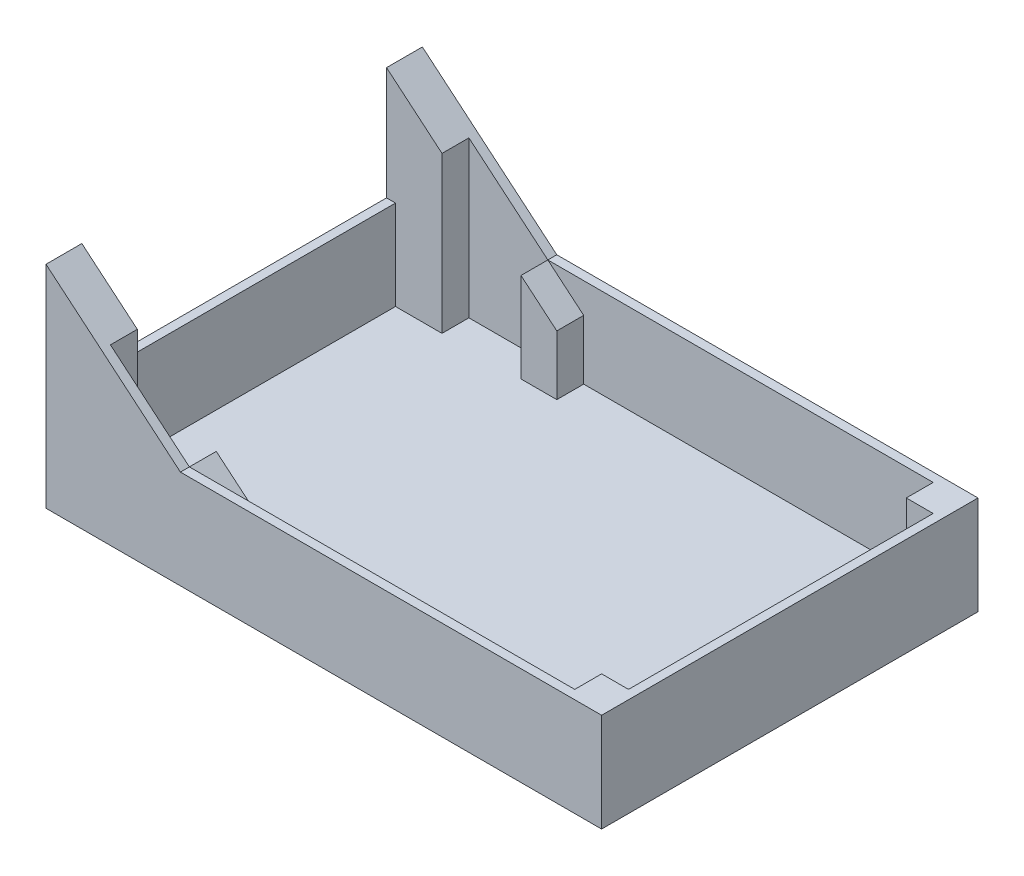
SolidWorks part; units mm, degrees
ref_plane "Front Plane" through (0, 0, 0) normal (0, 0, 1) x (1, 0, 0)
ref_plane "Top Plane" through (0, 0, 0) normal (0, 1, 0) x (1, 0, 0)
ref_plane "Right Plane" through (0, 0, 0) normal (1, 0, 0) x (0, 0, -1)
sketch "Sketch1" plane through (0, 0, 0) normal (0, 1, 0) x (1, 0, 0)
  line L1 (-60, 40) -> (60, 40)
  line L2 (-60, 40) -> (-60, -40)
  line L3 (-60, -40) -> (60, -40)
  line L4 (60, 40) -> (60, -40)
  line L5 (-60, 40) -> (60, -40) construction
  line L6 (-60, -40) -> (60, 40) construction
  point P0 (0, 0)
  dimension "D1" = 120
  dimension "D2" = 80
extrude "Extrude-Thin1" add sketch "Sketch1" along normal blind 20 thin thin type one direction wall 2
sketch "Sketch2" plane through (0, 0, 0) normal (0, -1, 0) x (1, 0, 0)
  line L4 (62, -42) -> (62, 42)
  line L5 (62, 42) -> (-62, 42)
  line L6 (-62, 42) -> (-62, -42)
  line L7 (-62, -42) -> (62, -42)
  line L8 (62, -42) -> (62, 42)
  line L9 (62, 42) -> (-62, 42)
  line L10 (-62, 42) -> (-62, -42)
  line L11 (-62, -42) -> (62, -42)
  dimension "D1" = 0
extrude "Boss-Extrude1" add sketch "Sketch2" along normal blind 2 contours L8 L9 L10 L11
sketch "Sketch3" plane through (0, 0, -40) normal (0, 0, 1) x (1, 0, 0)
  line L2 (-24, 13.2872) -> (-24, -2)
  line L3 (-24, -2) -> (-32, -2)
  line L4 (-32, 20) -> (-32, -2)
  line L5 (-62, 20) -> (-62, -2) construction
  line L6 (-62, -2) -> (62, -2) construction
  line L7 (-32, 20) -> (-24, 13.2872)
  dimension "D1" = 8
  dimension "D3" = 30
extrude "Boss-Extrude2" add sketch "Sketch3" along normal blind 6
ref_plane "Plane1" through (0, 0, 0) normal (0, 0, -1) x (-1, 0, 0)
sketch "Sketch9" plane through (0, 20, 0) normal (0, 1, 0) x (1, 0, 0)
  line L1 (60, 40) -> (54, 40)
  line L2 (60, 40) -> (60, 34)
  line L3 (60, 34) -> (54, 34)
  line L4 (54, 40) -> (54, 34)
  line L5 (60, -40) -> (54, -40)
  line L6 (60, -40) -> (60, -34)
  line L7 (60, -34) -> (54, -34)
  line L8 (54, -40) -> (54, -34)
  dimension "D1" = 6
  dimension "D2" = 6
  dimension "D3" = 6
  dimension "D4" = 6
extrude "Boss-Extrude7" add sketch "Sketch9" against normal up to surface (20 mm away) up to face at (-14, 0, -18.5)
sketch "Sketch10" plane through (0, 0, -42) normal (0, 0, -1) x (-1, 0, 0)
  line L0 (62, 20) -> (62, 45.173)
  line L1 (62, 45.173) -> (32, 20)
  line L2 (-62, 20) -> (62, 20) construction
  line L3 (32, 20) -> (62, 20)
  dimension "D1" = 40
extrude "Boss-Extrude8" add sketch "Sketch10" against normal blind 2
sketch "Sketch11" plane through (0, 0, -42) normal (0, 0, -1) x (-1, 0, 0)
  line L1 (62, 45.173) -> (32, 20) construction
  line L4 (62, 45.173) -> (49.619, 34.7841)
  line L5 (62, 45.173) -> (62, -2)
  line L6 (62, -2) -> (-62, -2) construction
  line L7 (49.619, -2) -> (62, -2)
  line L8 (49.619, 34.7841) -> (49.619, -2)
  line L9 (62, 45.173) -> (62, -2) construction
  dimension "D1" = 23
extrude "Boss-Extrude9" add sketch "Sketch11" against normal blind 6 from offset 2 offset against normal yes
mirror "Mirror1" about plane through (0, 0, 0) normal (0, 0, -1) of "Boss-Extrude9", "Boss-Extrude8", "Boss-Extrude2"
